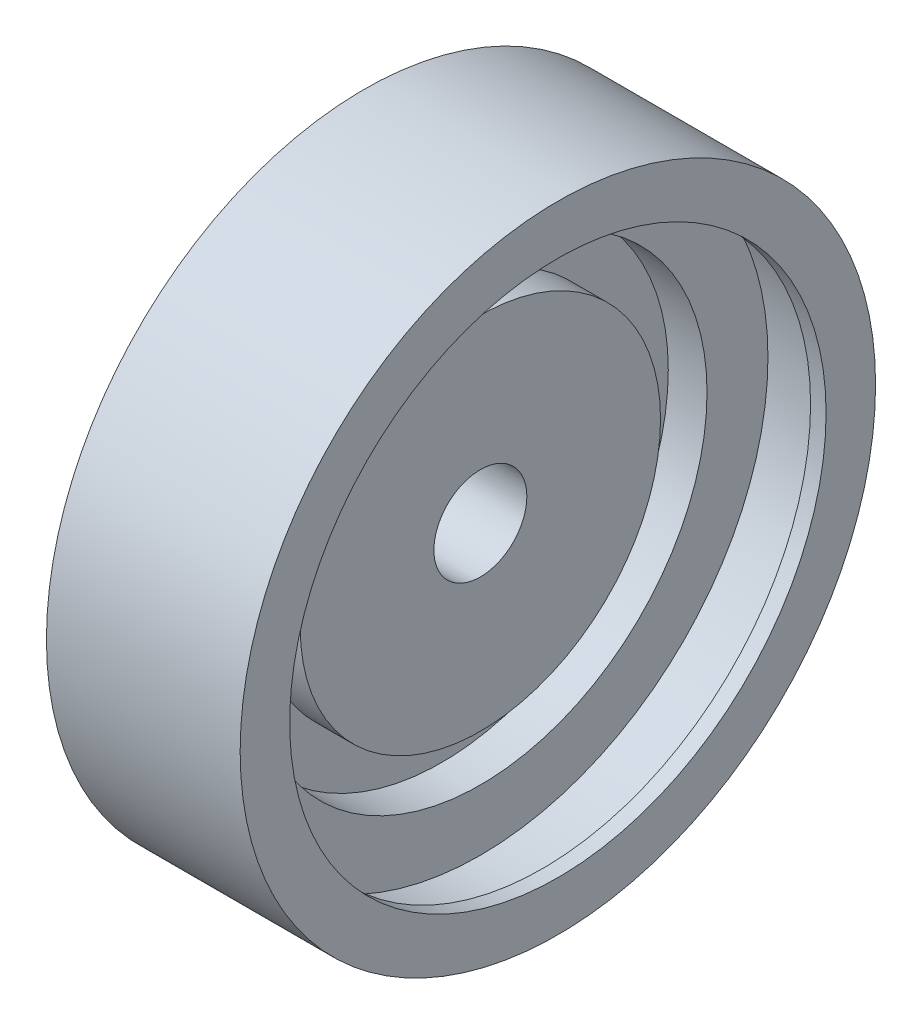
SolidWorks part; units mm, degrees
ref_plane "Alzado" through (0, 0, 0) normal (0, 0, 1) x (1, 0, 0)
ref_plane "Planta" through (0, 0, 0) normal (0, 1, 0) x (1, 0, 0)
ref_plane "Vista lateral" through (0, 0, 0) normal (1, 0, 0) x (0, 0, -1)
sketch "Croquis1" plane through (0, 0, 0) normal (1, 0, 0) x (0, 0, -1)
  circle A8 centre (0, 26) radius 11.1125
  circle A9 centre (0, 26) radius 3.175
  circle A10 centre (0, 26) radius 2.5
  circle A11 centre (0, 26) radius 15
  circle A12 centre (0, 0) radius 37.1125
  circle A13 centre (0, 0) radius 41
extrude "Saliente-Extruir1" add sketch "Croquis1" along normal blind 10 contours A11 A13 A12 | A12 A11 region at (0, 38.2955, 0) region at (0, 28.1714, -28.1714)
sketch "Croquis2" plane through (0, 0, 0) normal (-1, 0, 0) x (0, 0, 1)
  circle A0 centre (0, 0) radius 41
extrude "Saliente-Extruir2" add sketch "Croquis2" along normal blind 10
sketch "Croquis3" plane through (0, 0, 0) normal (1, 0, 0) x (0, 0, -1)
  line L1 (0, 0) -> (0, 14.8875)
  circle A10 centre (0, 0) radius 29.25
  circle A11 centre (0, 0) radius 23.25
  dimension "D1" = 46.5
  dimension "D2" = 58.5
extrude "Cortar-Extruir3" cut sketch "Croquis3" against normal blind 5 contours A10 A11 region at (0, 0, 28.4227)
sketch "Croquis6" plane through (-10, 0, 0) normal (-1, 0, 0) x (0, 0, 1)
  circle A0 centre (0, 0) radius 41
extrude "Saliente-Extruir4" add sketch "Croquis6" along normal blind 5
sketch "Croquis8" plane through (10, 0, 0) normal (1, 0, 0) x (0, 0, -1)
  circle A0 centre (0, 0) radius 41
  circle A1 centre (0, 0) radius 34.6125
  dimension "D1" = 69.225
extrude "Saliente-Extruir9" add sketch "Croquis8" against normal blind 2
sketch "Croquis9" plane through (0, 0, 0) normal (1, 0, 0) x (0, 0, -1)
  circle A0 centre (0, 0) radius 6
  dimension "D1" = 12
extrude "Cortar-Extruir4" cut sketch "Croquis9" against normal blind 22
